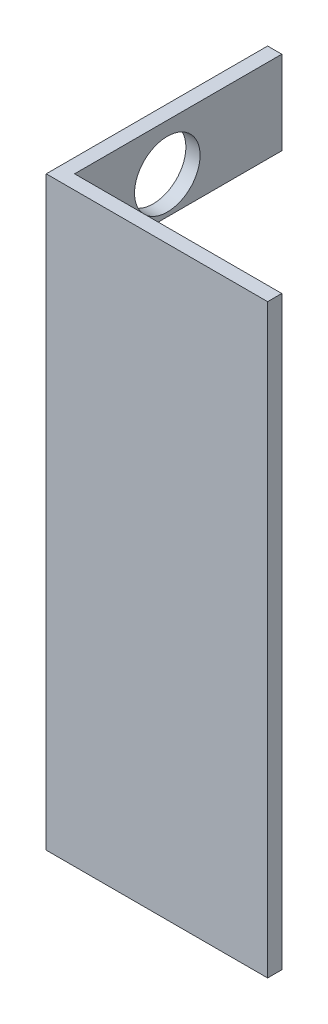
SolidWorks part; units mm, degrees
ref_plane "Front Plane" through (0, 0, 0) normal (0, 0, 1) x (1, 0, 0)
ref_plane "Top Plane" through (0, 0, 0) normal (0, 1, 0) x (1, 0, 0)
ref_plane "Right Plane" through (0, 0, 0) normal (1, 0, 0) x (0, 0, -1)
sketch "Sketch1" plane through (0, 0, 0) normal (0, 1, 0) x (1, 0, 0)
  line L0 (0, 0) -> (15.875, 0)
  line L1 (0, 0) -> (0, 15.875)
  line L2 (1.016, 1.016) -> (15.875, 1.016)
  line L3 (1.016, 1.016) -> (1.016, 15.875)
  line L4 (0, 15.875) -> (1.016, 15.875)
  line L5 (15.875, 1.016) -> (15.875, 0)
  dimension "D1" = 15.875
  dimension "D2" = 15.875
  dimension "D3" = 1.016
extrude "Boss-Extrude1" add sketch "Sketch1" along normal blind 42 contours L2 L5 L0 L1 L4 L3
sketch "Sketch4" plane through (1.016, 0, 0) normal (1, 0, 0) x (0, 0, -1)
  line L0 (15.875, 36) -> (1.016, 36)
  line L1 (15.875, 42) -> (15.875, 0) construction
  line L2 (1.016, 42) -> (1.016, 0) construction
  line L3 (1.016, 36) -> (1.016, 6)
  line L4 (1.016, 6) -> (15.875, 6)
  line L5 (15.875, 6) -> (15.875, 36)
  line L6 (15.875, 21) -> (1.016, 21) construction
  dimension "D1" = 30
extrude "Cut-Extrude2" cut sketch "Sketch4" against normal blind 6.35
sketch "Sketch6" plane through (1.016, 0, 0) normal (1, 0, 0) x (0, 0, -1)
  line L0 (1.016, 42) -> (1.016, 36) construction
  line L1 (1.016, 42) -> (15.875, 42) construction
  line L2 (1.016, 6) -> (1.016, 36) construction
  line L3 (1.016, 6) -> (1.016, 36)
  line L4 (1.016, 21) -> (11.5946, 21) construction
  circle A0 centre (7.666, 38.65) radius 2.35
  circle A1 centre (7.666, 3.35) radius 2.35
  dimension "D1" = 4.7
  dimension "D2" = 6.65
  dimension "D3" = 3.35
extrude "Cut-Extrude3" cut sketch "Sketch6" against normal blind 6.35 contours A1 | A0 region at (1.016, 3.35, -7.666)
